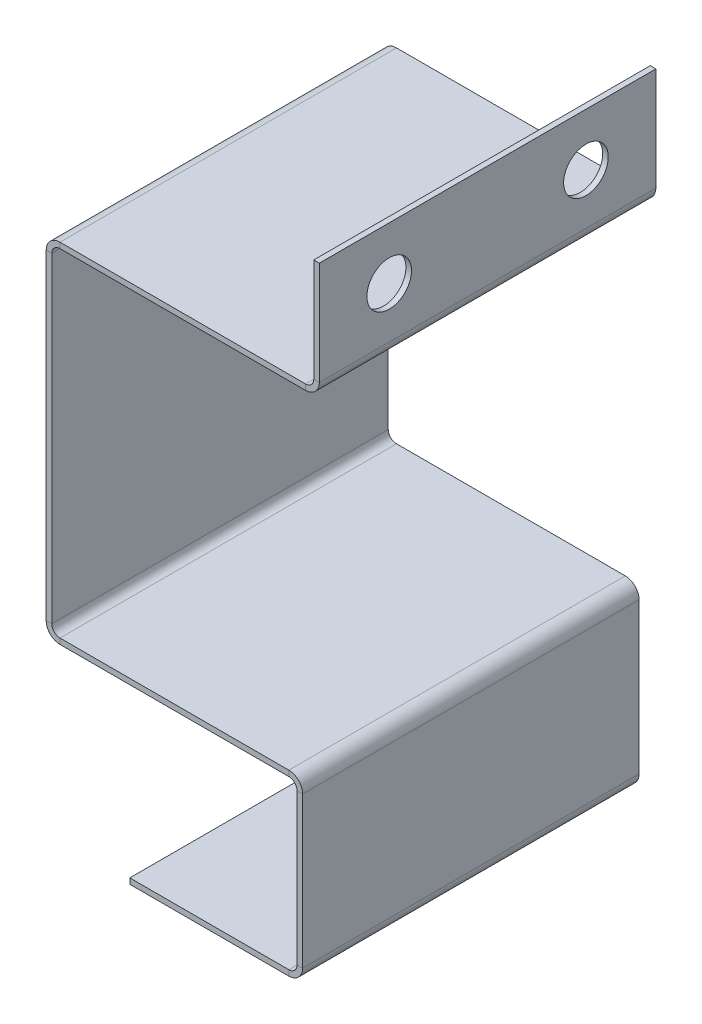
SolidWorks part; units mm, degrees
note: The reader was unsure of these and kept them because the rebuilt part matched: flange length of "Edge-Flange1", "Edge-Flange2", "Edge-Flange6", "Edge-Flange7", "Edge-Flange8".
ref_plane "Front Plane" through (0, 0, 0) normal (0, 0, 1) x (1, 0, 0)
ref_plane "Top Plane" through (0, 0, 0) normal (0, 1, 0) x (1, 0, 0)
ref_plane "Right Plane" through (0, 0, 0) normal (1, 0, 0) x (0, 0, -1)
sketch "Sketch1" plane through (0, 0, 0) normal (0, 1, 0) x (1, 0, 0)
  line L1 (-7.5, 15.0907) -> (7.5, 15.0907)
  line L2 (-7.5, 15.0907) -> (-7.5, -15.0907)
  line L3 (-7.5, -15.0907) -> (7.5, -15.0907)
  line L4 (7.5, 15.0907) -> (7.5, -15.0907)
  line L5 (-7.5, 15.0907) -> (7.5, -15.0907) construction
  line L6 (-7.5, -15.0907) -> (7.5, 15.0907) construction
  point P0 (0, 0)
base flange "Base-Flange2" sketch "Sketch1" thickness 0.5 reverse thickness direction yes parameters "D1"=0.7366
edge flange "Edge-Flange1" sketch "Sketch18" flange angle 90 flange length 15 flange position material outside bend radius 0.7366 thickness 0.5 relief rectangular parameters "D6"=10
sketch "Sketch18" plane through (7.5, 0.5, 0) normal (1, 0, 0) x (0, 0, -1)
  line L0 (-15.0907, 0) -> (15.0907, 0) construction
  line L1 (-15.0907, 0) -> (15.0907, 0)
  line L2 (-15.0907, 0) -> (-15.0907, 15)
  line L3 (-15.0907, 15) -> (15.0907, 15)
  line L4 (15.0907, 15) -> (15.0907, 0)
bend "EdgeBend1" bend radius 0.7366 bend angle 90 parameters "D5"=1
edge flange "Edge-Flange2" sketch "Sketch23" flange angle 90 flange length 22 flange position material outside bend radius 0.7366 thickness 0.5 relief rectangular parameters "D6"=10
sketch "Sketch23" plane through (7.5, 15.5, 0) normal (0, -1, 0) x (0, 0, 1)
  line L1 (15.0907, 0) -> (-15.0907, 0) construction
  line L2 (-15.0907, 0) -> (-15.0907, 22)
  line L3 (-15.0907, 22) -> (15.0907, 22)
  line L4 (15.0907, 22) -> (15.0907, 0)
  line L5 (15.0907, 0) -> (-15.0907, 0)
bend "EdgeBend2" bend radius 0.7366 bend angle 90 parameters "D5"=2
edge flange "Edge-Flange6" sketch "Sketch43" flange angle 90 flange length 30.25 flange position material outside bend radius 0.7366 thickness 0.5 relief rectangular parameters "D6"=10
sketch "Sketch43" plane through (-14.5, 16, 0) normal (1, 0, 0) x (0, 0, -1)
  line L1 (15.0907, 0) -> (-15.0907, 0) construction
  line L2 (-15.0907, 0) -> (-15.0907, 30.25)
  line L3 (-15.0907, 30.25) -> (15.0907, 30.25)
  line L4 (15.0907, 30.25) -> (15.0907, 0)
  line L5 (15.0907, 0) -> (-15.0907, 0)
bend "EdgeBend6" bend radius 0.7366 bend angle 90 parameters "D5"=3
edge flange "Edge-Flange7" sketch "Sketch48" flange angle 90 flange length 23.5 flange position material outside bend radius 0.7366 thickness 0.5 relief rectangular parameters "D6"=10
sketch "Sketch48" plane through (-14.5, 46.25, 0) normal (0, -1, 0) x (0, 0, -1)
  line L1 (15.0907, 0) -> (-15.0907, 0) construction
  line L2 (-15.0907, 0) -> (-15.0907, 23.5)
  line L3 (-15.0907, 23.5) -> (15.0907, 23.5)
  line L4 (15.0907, 23.5) -> (15.0907, 0)
  line L5 (15.0907, 0) -> (-15.0907, 0)
bend "EdgeBend7" bend radius 0.7366 bend angle 90 parameters "D5"=4
edge flange "Edge-Flange8" sketch "Sketch55" flange angle 90 flange length 10 flange position material outside bend radius 0.7366 thickness 0.5 relief rectangular parameters "D6"=10
sketch "Sketch55" plane through (9, 46.75, 0) normal (-1, 0, 0) x (0, 0, 1)
  line L1 (15.0907, 0) -> (-15.0907, 0) construction
  line L2 (-15.0907, 0) -> (-15.0907, 10)
  line L3 (-15.0907, 10) -> (15.0907, 10)
  line L4 (15.0907, 10) -> (15.0907, 0)
  line L5 (15.0907, 0) -> (-15.0907, 0)
bend "EdgeBend8" bend radius 0.7366 bend angle 90 parameters "D5"=5
sketch "Sketch58" plane through (9, 0, 0) normal (-1, 0, 0) x (0, 0, 1)
  line L0 (0, 64) -> (0, 74.0432) construction
  circle A0 centre (8.8222, 52.0368) radius 2
  circle A1 centre (-8.8222, 52.0368) radius 2
extrude "Cut-Extrude1" cut sketch "Sketch58" against normal through all normal cut yes
sketch "Bend-Lines3" plane through (0, 0, 0) normal (0, 1, 0) x (1, 0, 0)
sketch "Bounding-Box3" plane through (0, 0, 0) normal (0, 1, 0) x (1, 0, 0)
sheet metal parameters "Sheet-Metal(2)" thickness 0.5 parameters "D1"=0.7366
flat pattern "Flat-Pattern(2)" [suppressed]
sketch "Bend-Lines4" plane through (0, 0, 0) normal (0, 1, 0) x (1, 0, 0)
sketch "Bounding-Box4" [suppressed] plane through (0, 0, 0) normal (0, 1, 0) x (1, 0, 0)
sheet metal parameters "Sheet-Metal(3)" thickness 0.5 parameters "D1"=0.7366
flat pattern "Flat-Pattern(2)" [suppressed]
sketch "Bend-Lines5" plane through (0, 0, 0) normal (0, 1, 0) x (1, 0, 0)
sketch "Bounding-Box5" [suppressed] plane through (0, 0, 0) normal (0, 1, 0) x (1, 0, 0)
bend of the flat pattern "Flatten-<EdgeBend1>1"
sheet metal parameters "Sheet-Metal(4)" thickness 0.5 parameters "D1"=0.7366
flat pattern "Flat-Pattern(2)" [suppressed]
sketch "Bend-Lines6" plane through (0, 0, 0) normal (0, 1, 0) x (1, 0, 0)
sketch "Bounding-Box6" [suppressed] plane through (0, 0, 0) normal (0, 1, 0) x (1, 0, 0)
bend of the flat pattern "Flatten-<EdgeBend1>2"
bend of the flat pattern "Flatten-<EdgeBend2>1"
sheet metal parameters "Sheet-Metal(8)" thickness 0.5 parameters "D1"=0.7366
flat pattern "Flat-Pattern(2)" [suppressed]
sketch "Bend-Lines10" plane through (0, 0, 0) normal (0, 1, 0) x (1, 0, 0)
sketch "Bounding-Box10" [suppressed] plane through (0, 0, 0) normal (0, 1, 0) x (1, 0, 0)
bend of the flat pattern "Flatten-<EdgeBend1>6"
bend of the flat pattern "Flatten-<EdgeBend2>5"
bend of the flat pattern "Flatten-<EdgeBend6>1"
sheet metal parameters "Sheet-Metal(9)" thickness 0.5 parameters "D1"=0.7366
flat pattern "Flat-Pattern(2)" [suppressed]
sketch "Bend-Lines11" plane through (0, 0, 0) normal (0, 1, 0) x (1, 0, 0)
sketch "Bounding-Box11" [suppressed] plane through (0, 0, 0) normal (0, 1, 0) x (1, 0, 0)
bend of the flat pattern "Flatten-<EdgeBend1>7"
bend of the flat pattern "Flatten-<EdgeBend2>6"
bend of the flat pattern "Flatten-<EdgeBend6>2"
bend of the flat pattern "Flatten-<EdgeBend7>1"
sheet metal parameters "Sheet-Metal(10)" thickness 0.5 parameters "D1"=0.7366
flat pattern "Flat-Pattern(2)" [suppressed]
sketch "Bend-Lines12" plane through (0, 0, 0) normal (0, 1, 0) x (1, 0, 0)
sketch "Bounding-Box12" [suppressed] plane through (0, 0, 0) normal (0, 1, 0) x (1, 0, 0)
bend of the flat pattern "Flatten-<EdgeBend1>8"
bend of the flat pattern "Flatten-<EdgeBend2>7"
bend of the flat pattern "Flatten-<EdgeBend6>3"
bend of the flat pattern "Flatten-<EdgeBend7>2"
bend of the flat pattern "Flatten-<EdgeBend8>1"
sheet metal parameters "Sheet-Metal(11)" thickness 0.5 parameters "D1"=0.7366
flat pattern "Flat-Pattern(2)" [suppressed]
sketch "Bend-Lines13" plane through (0, 0, 0) normal (0, 1, 0) x (1, 0, 0)
sketch "Bounding-Box13" [suppressed] plane through (0, 0, 0) normal (0, 1, 0) x (1, 0, 0)
bend of the flat pattern "Flatten-<EdgeBend1>9"
bend of the flat pattern "Flatten-<EdgeBend2>8"
bend of the flat pattern "Flatten-<EdgeBend6>4"
bend of the flat pattern "Flatten-<EdgeBend7>3"
bend of the flat pattern "Flatten-<EdgeBend8>2"
